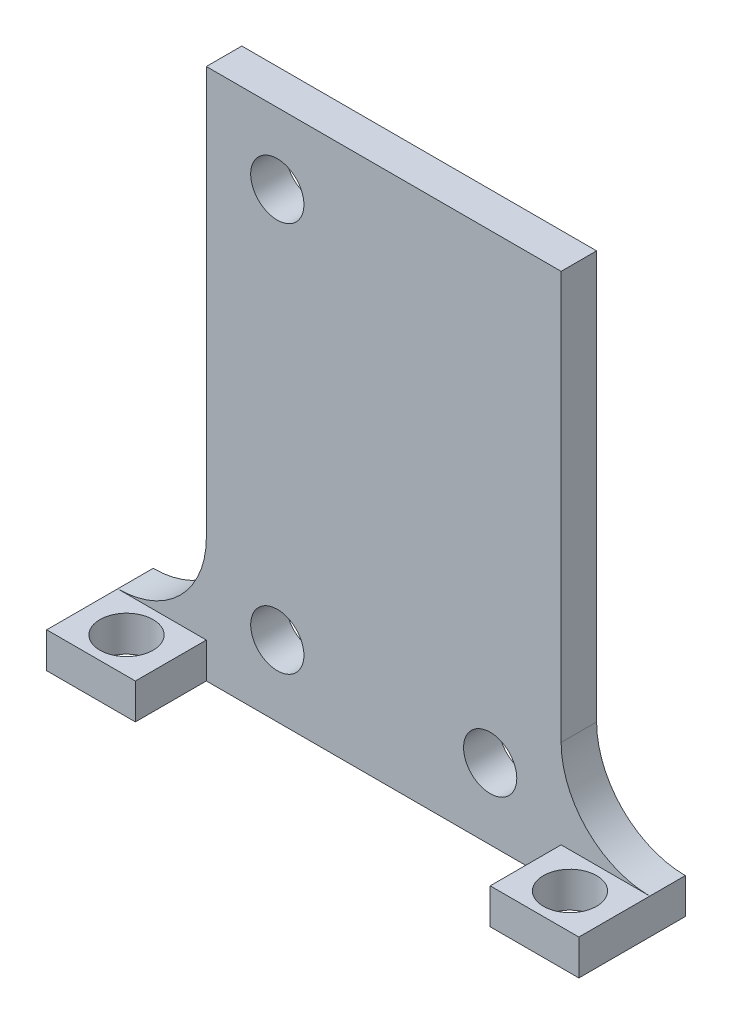
SolidWorks part; units mm, degrees
ref_plane "Front Plane" through (0, 0, 0) normal (0, 0, 1) x (1, 0, 0)
ref_plane "Top Plane" through (0, 0, 0) normal (0, 1, 0) x (1, 0, 0)
ref_plane "Right Plane" through (0, 0, 0) normal (1, 0, 0) x (0, 0, -1)
sketch "Sketch1" plane through (0, 0, 0) normal (0, 0, 1) x (1, 0, 0)
  line L1 (-12.7, -19.05) -> (12.7, -19.05)
  line L2 (-12.7, -19.05) -> (-12.7, 19.05)
  line L3 (-12.7, 19.05) -> (12.7, 19.05)
  line L4 (12.7, -19.05) -> (12.7, 19.05)
  line L5 (-12.7, -19.05) -> (12.7, 19.05) construction
  line L6 (-12.7, 19.05) -> (12.7, -19.05) construction
  circle A0 centre (-7.62, 13.97) radius 1.905
  circle A1 centre (-7.62, -13.97) radius 1.905
  circle A2 centre (7.62, -13.97) radius 1.905
  circle A3 centre (0, -19.05) radius 44.45 construction
  point P0 (0, 0)
  point P12 (0, 0)
  point P13 (0, -19.05)
  dimension "D7" = 3.81
  dimension "D8" = 88.9
  dimension "D1" = 25.4
  dimension "D2" = 38.1
  dimension "D3" = 5.08
  dimension "D4" = 5.08
  dimension "D5" = 5.08
  dimension "D6" = 5.08
extrude "Boss-Extrude1" add sketch "Sketch1" along normal mid plane 2.54
sketch "Sketch2" plane through (0, -19.05, 0) normal (0, -1, 0) x (1, 0, 0)
  line L0 (-12.7, 1.27) -> (-12.7, -1.27) construction
  line L1 (-12.7, 6.35) -> (-19.05, 6.35)
  line L2 (-12.7, 6.35) -> (-12.7, -1.27)
  line L3 (-12.7, -1.27) -> (-19.05, -1.27)
  line L4 (-19.05, 6.35) -> (-19.05, -1.27)
  line L5 (-12.7, -1.27) -> (12.7, -1.27) construction
  circle A0 centre (-15.875, 3.81) radius 1.905
  point P12 (0, 0)
  point P13 (-15.875, -1.27)
  dimension "D3" = 3.81
  dimension "D1" = 7.62
  dimension "D2" = 6.35
  dimension "D4" = 5.08
extrude "Boss-Extrude2" add sketch "Sketch2" against normal blind 2.54
mirror "Mirror5" about plane through (0, 0, 0) normal (1, 0, 0) of "Boss-Extrude2"
fillet "Fillet1" radius 6.35 2 edges at (-12.7, -16.51, 0) (12.7, -16.51, 0)
